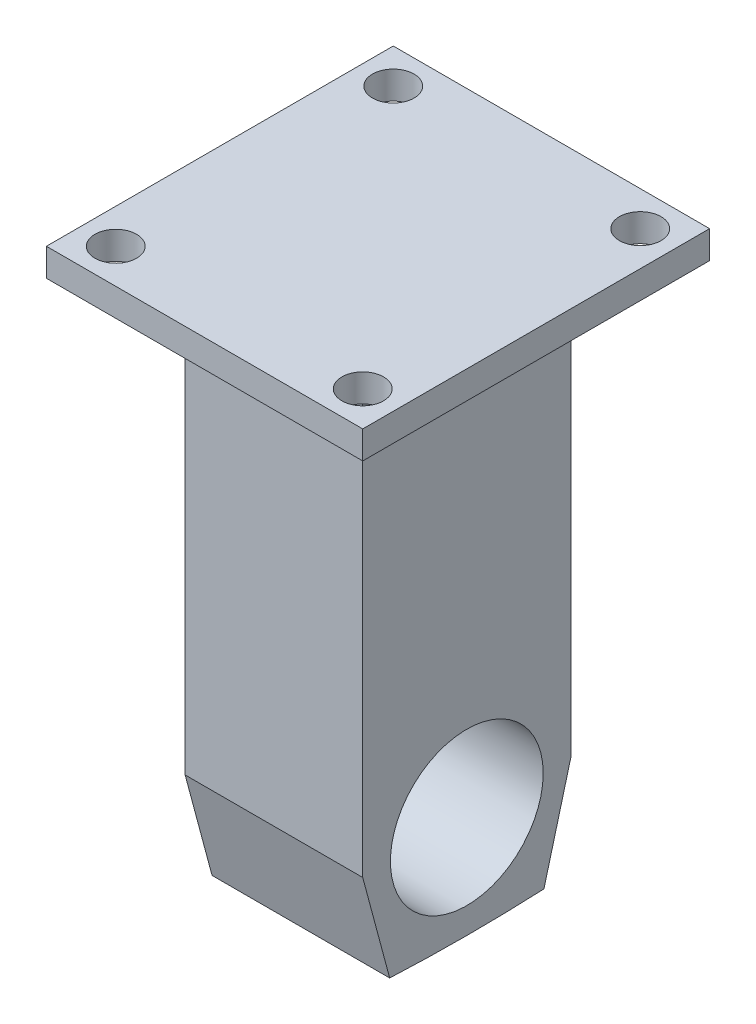
SolidWorks part; units mm, degrees
material "ABS"
ref_plane "Front Plane" through (0, 0, 0) normal (0, 0, 1) x (1, 0, 0)
ref_plane "Top Plane" through (0, 0, 0) normal (0, 1, 0) x (1, 0, 0)
ref_plane "Right Plane" through (0, 0, 0) normal (1, 0, 0) x (0, 0, -1)
sketch "Sketch1" plane through (0, 0, 0) normal (0, 1, 0) x (1, 0, 0)
  line L1 (-16.256, -19.05) -> (16.256, -19.05)
  line L2 (-16.256, -19.05) -> (-16.256, 19.05)
  line L3 (-16.256, 19.05) -> (16.256, 19.05)
  line L4 (16.256, -19.05) -> (16.256, 19.05)
  line L5 (-16.256, -19.05) -> (16.256, 19.05) construction
  line L6 (-16.256, 19.05) -> (16.256, -19.05) construction
  point P0 (0, 0)
extrude "Boss-Extrude1" add sketch "Sketch1" along normal blind 78.74
sketch "Sketch2" plane through (16.256, 0, 0) normal (1, 0, 0) x (0, 0, -1)
  line L0 (-19.05, 0) -> (-14.1195, -18.4009)
  line L1 (19.05, 0) -> (14.1195, -18.4009)
  line L2 (-19.05, 0) -> (19.05, 0)
  line L3 (-19.05, 0) -> (19.05, 0) construction
  arc A1 (14.1195, -18.4009) -> (-14.1195, -18.4009) centre (0, 281.2546) cw
  dimension "D1" = 19.05
  dimension "D2" = 19.05
  dimension "D3" = 75
  dimension "D4" = 75
extrude "Boss-Extrude2" add sketch "Sketch2" against normal up to vertex (32.512 mm away) contours L0 A1 L1 L2 up to point (-16.256, 0, -19.05)
sketch "Sketch3" plane through (16.256, 0, 0) normal (1, 0, 0) x (0, 0, -1)
  circle A0 centre (0, 0) radius 13.9872
extrude "Cut-Extrude1" cut sketch "Sketch3" against normal blind 127 contours A0
sketch "Sketch4" plane through (0, 78.74, 0) normal (0, 1, 0) x (1, 0, 0)
  line L1 (28.956, -31.75) -> (-28.956, -31.75)
  line L2 (28.956, -31.75) -> (28.956, 31.75)
  line L3 (28.956, 31.75) -> (-28.956, 31.75)
  line L4 (-28.956, -31.75) -> (-28.956, 31.75)
  line L5 (28.956, -31.75) -> (-28.956, 31.75) construction
  line L6 (28.956, 31.75) -> (-28.956, -31.75) construction
  point P0 (0, 0)
extrude "Boss-Extrude3" add sketch "Sketch4" along normal blind 5.08
sketch "Sketch5" plane through (0, 83.82, 0) normal (0, 1, 0) x (1, 0, 0)
  line L0 (0, -31.75) -> (0, 31.75) construction
  line L1 (28.956, 31.75) -> (-28.956, 31.75) construction
  line L2 (-28.956, 0) -> (28.956, 0) construction
  line L3 (28.956, -31.75) -> (28.956, 31.75) construction
  line L4 (-22.606, -31.75) -> (-22.606, 31.75) construction
  line L5 (-28.956, 25.4) -> (28.956, 25.4) construction
  line L6 (-28.956, 31.75) -> (-28.956, -31.75) construction
  circle A0 centre (-22.606, 25.4) radius 3.81
  circle A1 centre (-22.606, -25.4) radius 3.81
  circle A2 centre (22.606, 25.4) radius 3.81
  circle A3 centre (22.606, -25.4) radius 3.81
  point P6 (0, 0)
  point P12 (0, 0)
  point P15 (-22.606, 0)
  point P18 (0, 25.4)
  point P20 (-22.606, 25.4)
  dimension "D1" = 6.35
  dimension "D2" = 6.35
  dimension "D3" = 0
extrude "Cut-Extrude2" cut sketch "Sketch5" against normal blind 5.08
